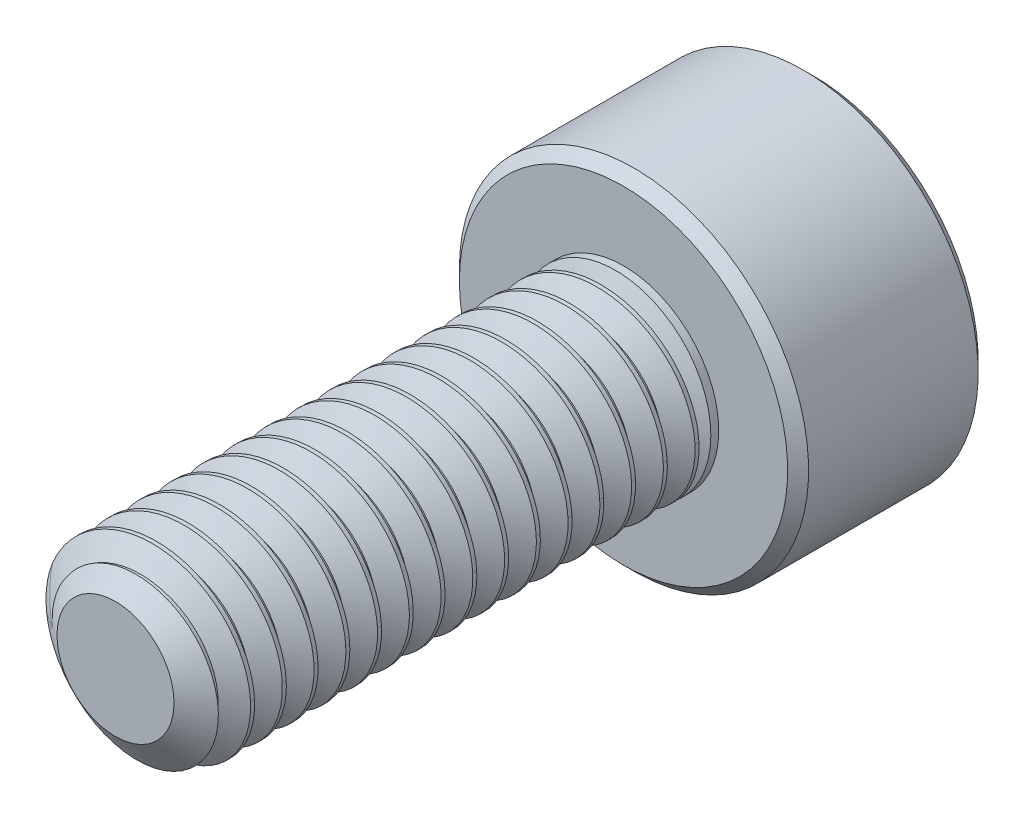
SolidWorks part; units mm, degrees
ref_plane "Front Plane" through (0, 0, 0) normal (0, 0, 1) x (1, 0, 0)
ref_plane "Top Plane" through (0, 0, 0) normal (0, 1, 0) x (1, 0, 0)
ref_plane "Right Plane" through (0, 0, 0) normal (1, 0, 0) x (0, 0, -1)
sketch "Sketch1" plane through (0, 0, 0) normal (0, 0, 1) x (1, 0, 0)
  circle A0 centre (0, 0) radius 1.5
  dimension "OD" = 3
extrude "Extrude1" add sketch "Sketch1" against normal blind 8
sketch "Sketch2" plane through (0, 0, 0) normal (0, 0, 1) x (1, 0, 0)
  circle A0 centre (0, 0) radius 1.5 construction
  circle A1 centre (0, 0) radius 1.5
curve "Helix/Spiral1" pitch 0.5 height 8.5 radius 1.5 centre (0, 0, 0) axis (0, 0, -1) start towards (0, 1, 0) parameters "pitch"=0.5
sketch "Sketch3" plane through (0, 0, 0) normal (1, 0, 0) x (0, 0, -1)
  line L0 (-0.4375, 1.5) -> (-0.25, 1.1752)
  line L1 (-0.25, 1.1752) -> (-0.1875, 1.1752)
  line L2 (-0.1875, 1.1752) -> (0, 1.5)
  line L3 (-0.4375, 1.5) -> (0, 1.5)
  line L4 (-0.2188, 1.5) -> (-0.2188, 1.1752) construction
  line L5 (-0.3438, 1.3376) -> (-0.0938, 1.3376) construction
  line L6 (0, 1.5) -> (0, -1.5) construction
  line L7 (0, -1.5) -> (8, -1.5) construction
  point P11 (2.25, -1.5)
  dimension "D1" = 0.0625
  dimension "D2" = 0.25
  dimension "D3" = 60
  dimension "D4" = 2.25
sweep "Cut-Sweep1" cut profiles "Sketch3" path "Helix/Spiral1" align with end faces yes
sketch "Sketch4" plane through (0, 0, 0) normal (1, 0, 0) x (0, 0, -1)
  line L0 (0.4053, 1.5) -> (0, 0.9212)
  line L1 (0, 0.9212) -> (0, 1.5)
  line L2 (0.4053, 1.5) -> (0, 1.5)
  line L3 (-0.4375, 1.5) -> (0, 1.5) construction
  line L4 (0, 0) -> (7.0209, 0) construction
  dimension "D1" = 55
  dimension "D2" = 0.254
revolve "Cut-Revolve1" cut sketch "Sketch4" angle 360 about L4
sketch "Sketch5" plane through (0, 0, 0) normal (1, 0, 0) x (0, 0, -1)
  line L0 (8, -1.1822) -> (8, 1.0703) construction
  line L1 (8, 1.5) -> (0.1203, 1.5)
  line L2 (8, 1.5) -> (8, 0)
  line L3 (8, 0) -> (0.0001, 0)
  line L4 (0.0001, 1.1698) -> (0.0001, 0)
  line L5 (0.1203, 1.5) -> (0.0001, 1.1698)
  line L6 (0, 0) -> (9.9695, 0) construction
  point P3 (0.0001, 1.5)
  point P10 (0.0001, 1.5)
  dimension "D1" = 0.3302
  dimension "Thread min" = 0.0001
  dimension "D3" = 20
revolve "partially thread" [suppressed] add sketch "Sketch5" angle 360 about L6
sketch "Sketch6" plane through (0, 0, -8) normal (0, 0, -1) x (-1, 0, 0)
  circle A0 centre (0, 0) radius 2.75
  dimension "head dia" = 5.5
extrude "Extrude2" add sketch "Sketch6" along normal blind 3
sketch "Sketch7" plane through (0, 0, -11) normal (0, 0, -1) x (-1, 0, 0)
  line L1 (0, 1.4434) -> (-1.25, 0.7217)
  line L2 (-1.25, 0.7217) -> (-1.25, -0.7217)
  line L3 (-1.25, -0.7217) -> (0, -1.4434)
  line L4 (0, -1.4434) -> (1.25, -0.7217)
  line L5 (1.25, -0.7217) -> (1.25, 0.7217)
  line L6 (1.25, 0.7217) -> (0, 1.4434)
  circle A0 centre (0, 0) radius 1.25 construction
  dimension "hex dia" = 2.5
extrude "Cut-Extrude1" cut sketch "Sketch7" against normal blind 1.875
sketch "Sketch8" plane through (0, 0, -11) normal (0, 0, -1) x (-1, 0, 0)
  circle A0 centre (0, 0) radius 1.4434
extrude "Cut-Extrude2" cut sketch "Sketch8" against normal through all draft 45
chamfer "Chamfer1" distance 0.165 angle 45 2 edges at (-2.75, 0, -11) (-2.75, 0, -8)
sketch "Sketch9" plane through (0, 0, 0) normal (1, 0, 0) x (0, 0, -1)
  line L0 (0, 1.5) -> (0, -1.5) construction
  line L1 (2.75, 1.5) -> (2.75, -1.5) construction
  dimension "D1" = 2.75
sketch "Sketch10" plane through (0, 0, 0) normal (1, 0, 0) x (0, 0, -1)
  line L0 (8, 1.5) -> (8, 0)
  line L1 (8, 1.5) -> (7.875, 1.5)
  line L2 (7.875, 1.5) -> (7.2537, 0)
  line L3 (8, 0) -> (7.2537, 0)
  line L4 (8, 2.585) -> (8, -2.585) construction
  dimension "D1" = 22.5
  dimension "D2" = 0.125
revolve "Revolve1" add sketch "Sketch10" angle 360 about L3
equation "\"D3@Helix/Spiral1\" = \"screw length@Extrude1\"+\"pitch@Helix/Spiral1\""
equation "\"D1@Sketch3\" = \"pitch@Helix/Spiral1\"*.125"
equation "\"D2@Sketch3\" = \"pitch@Helix/Spiral1\"*.5"
equation "\"D1@Cut-Extrude1\" = \"hex dia@Sketch7\"*.75"
equation "\"D1@Chamfer1\" = \"head dia@Sketch6\"*.03"
equation "\"D1@Sketch9\" = \"pitch@Helix/Spiral1\"*5.5"
equation "\"D2@Sketch10\" = \"pitch@Helix/Spiral1\"*.25"
equation "\"D4@Sketch3\" = \"pitch@Helix/Spiral1\"*4.50"
